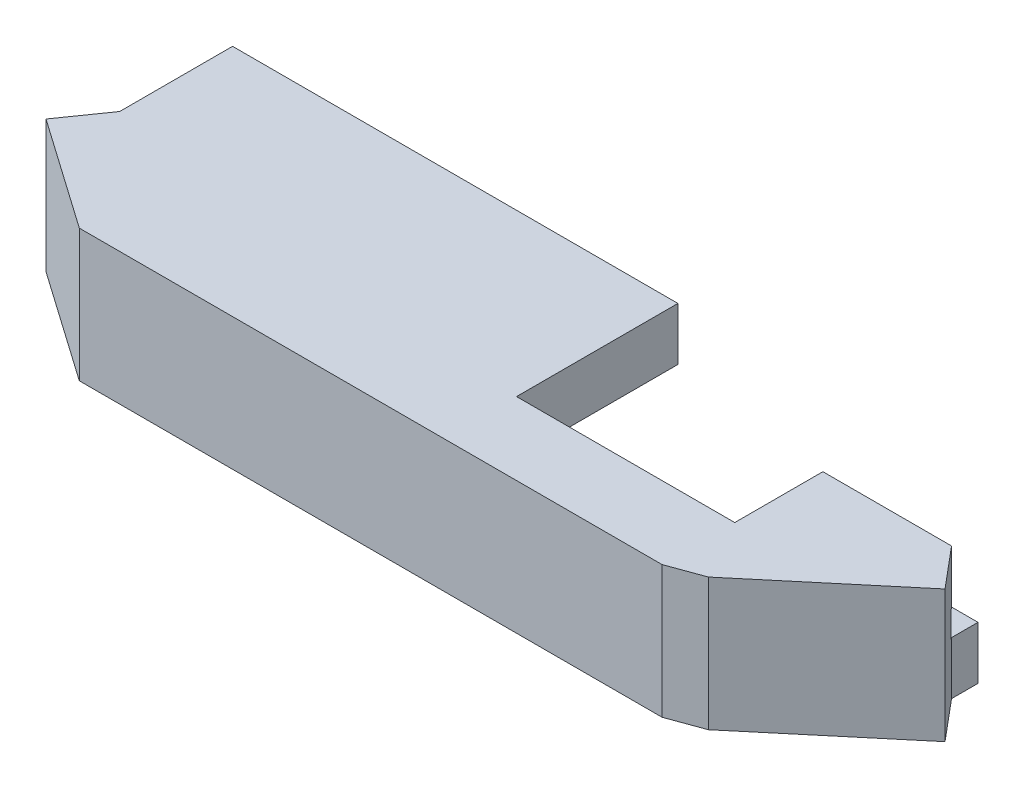
SolidWorks part; units mm, degrees
ref_plane "Front Plane" through (0, 0, 0) normal (0, 0, 1) x (1, 0, 0)
ref_plane "Top Plane" through (0, 0, 0) normal (0, 1, 0) x (1, 0, 0)
ref_plane "Right Plane" through (0, 0, 0) normal (1, 0, 0) x (0, 0, -1)
sketch "Sketch2" plane through (0, 0, 0) normal (0, 1, 0) x (1, 0, 0)
  line L0 (0.1914, 0) -> (8, 0)
  line L1 (0, 0) -> (-7.3724, 5.1622)
  line L2 (18.2588, -0.3) -> (0, -0.3)
  line L5 (18.3, 0) -> (42.8, 0)
  line L6 (8.2412, 0) -> (18.0588, 0)
  line L7 (42.8, -4) -> (0, -4)
  line L9 (18.2588, -0.3) -> (42.8, -0.3)
  line L10 (8.0412, 0) -> (8, 0)
  line L11 (8, 0) -> (8.0884, 0)
  line L12 (42.8, 0) -> (52.5288, 8.1634)
  line L15 (-9.6667, 1.8856) -> (-1.2612, -4)
  line L16 (-7.3724, 5.1622) -> (-7.5444, 4.9164)
  line L17 (-7.3724, 5.1622) -> (-9.6667, 1.8856)
  line L18 (18.2116, 0) -> (18.3, 0)
  line L19 (42.8, -0.3) -> (42.9928, -0.2298)
  line L20 (42.9928, -0.2298) -> (43.6395, 0.3128)
  line L22 (-7.3724, 5.1622) -> (-7.5444, 4.9164)
  line L23 (0, -4) -> (-1.2612, -4)
  line L24 (-7.5444, 4.9164) -> (-0.0946, -0.3)
  line L25 (18.3, 0) -> (27.9042, 0)
  line L26 (43.6395, 0.3128) -> (52.7216, 7.9336)
  line L28 (18.3, 0) -> (26.3, 0)
  line L33 (52.5288, 8.1634) -> (52.7216, 7.9336)
  line L35 (42.8, -4) -> (45.3712, -3.0642)
  line L36 (18.0588, -0.3) -> (18.0588, 0.6076)
  line L37 (13.15, 0) -> (13.15, 4.2)
  line L38 (13.15, 0) -> (13.15, 4.2)
  line L39 (8.2412, -0.3) -> (8.2412, 0.6076)
  line L40 (0.1282, 0) -> (0.58, 0)
  line L42 (0, -0.3) -> (-0.0946, -0.3)
  line L43 (45.3712, -3.0642) -> (55.0999, 5.0992)
  line L44 (0, 0) -> (0.1282, 0)
  line L45 (52.7216, 7.9336) -> (55.0999, 5.0992)
  line L46 (26.3, 1.5) -> (26.3, 13.7)
  line L47 (26.3, 13.7) -> (-7.3724, 13.7)
  line L48 (-7.3724, 5.1622) -> (-7.3724, 13.7)
  line L50 (42.8, 1.5) -> (26.3, 1.5)
  line L51 (42.8, 1.5) -> (42.8, 8.1634)
  line L52 (52.5288, 8.1634) -> (42.8, 8.1634)
  arc A2 (18.2588, -0.3) -> (8.0412, -0.3) centre (13.15, -0.95) ccw
  arc A3 (18.2588, 0) -> (8.0412, 0) centre (13.15, -0.65) ccw
  dimension "D2" = 9
  dimension "D3" = 8
  dimension "D4" = 24.5
  dimension "D5" = 4
  dimension "D6" = 12.7
  dimension "D7" = 140
  dimension "D9" = 10.3
  dimension "D12" = 0.3
  dimension "D13" = 145
  dimension "D14" = 4
  dimension "D15" = 90
  dimension "D16" = 8
  dimension "D18" = 4
  dimension "D20" = 0.3
  dimension "D21" = 13.7
  dimension "D22" = 1.5
extrude "Boss-Extrude1" add sketch "Sketch2" along normal blind 4 contours A3 L18 L5 L25 L12 L52 L51 L50 L46 L47 L48 L1 L44 L40 L0 L10 | L18 A3 L11 A2 | L37 A2 L39 L6 | L36 A2 L37 L6 | L39 L2 L36 L6 | L39 A2 L2 | L2 A2 L36 | A2 L9 L19 L20 L26 L33 L12 L5 L25 L18 | L45 L26 L20 L19 L9 L2 L42 L24 L17 L15 L23 L7 L35 L43 | A2 L11 L10 L0 L40 L44 L1 L16 L24 L42 L2 region at (14.1656, 0, -6.9861) region at (0.3857, 0, 0.1656) region at (13.15, 0, -4.3884) region at (8.1693, 0, -0.0217) region at (18.2794, 0, 0.0355) region at (23.1087, 0, 0.8992) region at (11.0876, 0, -1.7623) region at (18.1307, 0, -0.0217) region at (13.15, 0, 0.15) region at (15.2124, 0, -1.7623)
extrude "Boss-Extrude3" add sketch "Sketch2<4>" against normal blind 2 contours L45 L26 L20 L19 L9 L2 L42 L24 L17 L15 L23 L7 L35 L43 | L36 A2 L37 L6 | L37 A2 L39 L6 | L39 L2 L36 L6 region at (23.1087, 0, 0.8992) region at (11.0876, 0, -1.7623) region at (13.15, 0, 0.15) region at (15.2124, 0, -1.7623)
sketch "Sketch2<4>" plane through (0, 0, 0) normal (0, 1, 0) x (1, 0, 0) same geometry as "Sketch2"
ref_plane "Plane1" through (0, -2, 0) normal (0, -1, 0) x (-1, 0, 0)
sketch "Sketch3" plane through (0, -2, 0) normal (0, -1, 0) x (-1, 0, 0)
  line L0 (-52.5288, 8.1634) -> (-52.5288, 10.1634)
  line L2 (-52.5288, 10.1634) -> (-44.0288, 10.1634)
  line L5 (-44.0288, 10.1634) -> (-44.0288, 1.0311)
  line L6 (-18.2588, 0) -> (-18.2588, 5.1622)
  line L7 (7.3724, 5.1622) -> (-18.2588, 5.1622)
  line L34 (-18.3, 0) -> (-42.8, 0)
  line L41 (-44.0288, 8.1634) -> (-42.8, 8.1634)
  line L49 (-42.8, 1.5) -> (-42.8, 8.1634)
  line L53 (-42.8, 1.5) -> (-26.3, 1.5)
  line L54 (7.3724, 5.1622) -> (7.3724, 13.7)
  line L55 (-26.3, 13.7) -> (7.3724, 13.7)
  line L56 (-26.3, 1.5) -> (-26.3, 13.7)
  line L57 (-52.7216, 7.9336) -> (-55.0999, 5.0992)
  line L58 (0, 0) -> (-0.1282, 0)
  line L59 (-45.3712, -3.0642) -> (-55.0999, 5.0992)
  line L60 (0, -0.3) -> (0.0946, -0.3)
  line L61 (-0.1282, 0) -> (-0.58, 0)
  line L62 (-8.2412, -0.3) -> (-8.2412, 0.6076)
  line L63 (-13.15, 0) -> (-13.15, 4.2)
  line L64 (-13.15, 0) -> (-13.15, 4.2)
  line L65 (-18.0588, -0.3) -> (-18.0588, 0.6076)
  line L66 (-42.8, -4) -> (-45.3712, -3.0642)
  line L67 (-52.5288, 8.1634) -> (-52.7216, 7.9336)
  line L68 (-18.3, 0) -> (-26.3, 0)
  line L69 (-43.6395, 0.3128) -> (-52.7216, 7.9336)
  line L70 (-18.3, 0) -> (-27.9042, 0)
  line L71 (7.5444, 4.9164) -> (0.0946, -0.3)
  line L72 (0, -4) -> (1.2612, -4)
  line L73 (7.3724, 5.1622) -> (7.5444, 4.9164)
  line L74 (-42.9928, -0.2298) -> (-43.6395, 0.3128)
  line L75 (-42.8, -0.3) -> (-42.9928, -0.2298)
  line L76 (-18.2116, 0) -> (-18.3, 0)
  line L77 (7.3724, 5.1622) -> (9.6667, 1.8856)
  line L78 (7.3724, 5.1622) -> (7.5444, 4.9164)
  line L79 (9.6667, 1.8856) -> (1.2612, -4)
  line L80 (-42.8, 0) -> (-52.5288, 8.1634)
  line L81 (-8, 0) -> (-8.0884, 0)
  line L82 (-8.0412, 0) -> (-8, 0)
  line L83 (-18.2588, -0.3) -> (-42.8, -0.3)
  line L84 (-42.8, -4) -> (0, -4)
  line L85 (-8.2412, 0) -> (-18.0588, 0)
  line L86 (-18.2588, -0.3) -> (0, -0.3)
  line L87 (0, 0) -> (7.3724, 5.1622)
  line L88 (-0.1914, 0) -> (-8, 0)
  arc A4 (-18.2588, 0) -> (-8.0412, 0) centre (-13.15, -0.65) cw
  arc A5 (-18.2588, -0.3) -> (-8.0412, -0.3) centre (-13.15, -0.95) cw
  dimension "D1" = 2
  dimension "D2" = 8.5
extrude "Boss-Extrude4" add sketch "Sketch3" along normal blind 4 contours L6 A4 L81 L88 L61 L58 L87 L7 | L80 L5 L2 L0 | L83 A5 L76 L34 L80 L67 L69 L74 L75 | L86 L83 L75 L74 L69 L57 L59 L66 L84 L72 L79 L77 L71 L60 | A5 L63 L85 L62 | A5 L65 L85 L63 | A5 L62 L86 | L65 L86 L62 L85 | L81 A5 L86 L60 L71 L73 L87 L58 L61 L88 | A5 L81 A4 L76 | A5 L86 L65 region at (48.3016, -2, -4.57) region at (47.3711, -2, -6.9995) region at (23.1087, -2, 0.8992) region at (18.1307, -2, -0.0217) region at (13.15, -2, 0.15) region at (18.2352, -2, -0.1116) region at (4.5171, -2, -3.0985) region at (15.2124, -2, -1.7623) region at (8.1693, -2, -0.0217) region at (8.0206, -2, 0.1656) region at (11.0876, -2, -1.7623)
ref_plane "Plane2" through (0, -6, 0) normal (0, -1, 0) x (-1, 0, 0)
sketch "Sketch4" plane through (0, -6, 0) normal (0, -1, 0) x (-1, 0, 0)
  line L0 (-18.2588, 0) -> (-12.2588, 0)
  line L1 (-18.2588, 0) -> (-18.2588, 5.1907)
  line L2 (-18.2588, 5.1907) -> (-12.2588, 5.1622)
  line L3 (7.3724, 5.1622) -> (-18.2588, 5.1622) construction
  line L4 (-12.2588, 5.1622) -> (-12.2588, 0)
  dimension "D1" = 6
extrude "Cut-Extrude1" cut sketch "Sketch4" against normal blind 4
sketch "Sketch5" plane through (0, -6, 0) normal (0, -1, 0) x (-1, 0, 0)
  line L1 (-18.0588, 0) -> (-18.0588, 0.6076)
  line L2 (-18.0588, -0.3) -> (-18.0588, 0.6076) construction
  line L3 (-12.2588, 0) -> (-42.8, 0) construction
  line L6 (-18.0588, 0) -> (-12.2588, 0)
  line L7 (-12.2588, 0) -> (-12.2588, 4.1223)
  arc A2 (-12.2588, 4.1223) -> (-18.0588, 0.6076) centre (-13.15, -0.95) ccw
extrude "Boss-Extrude6" add sketch "Sketch5" against normal blind 4
